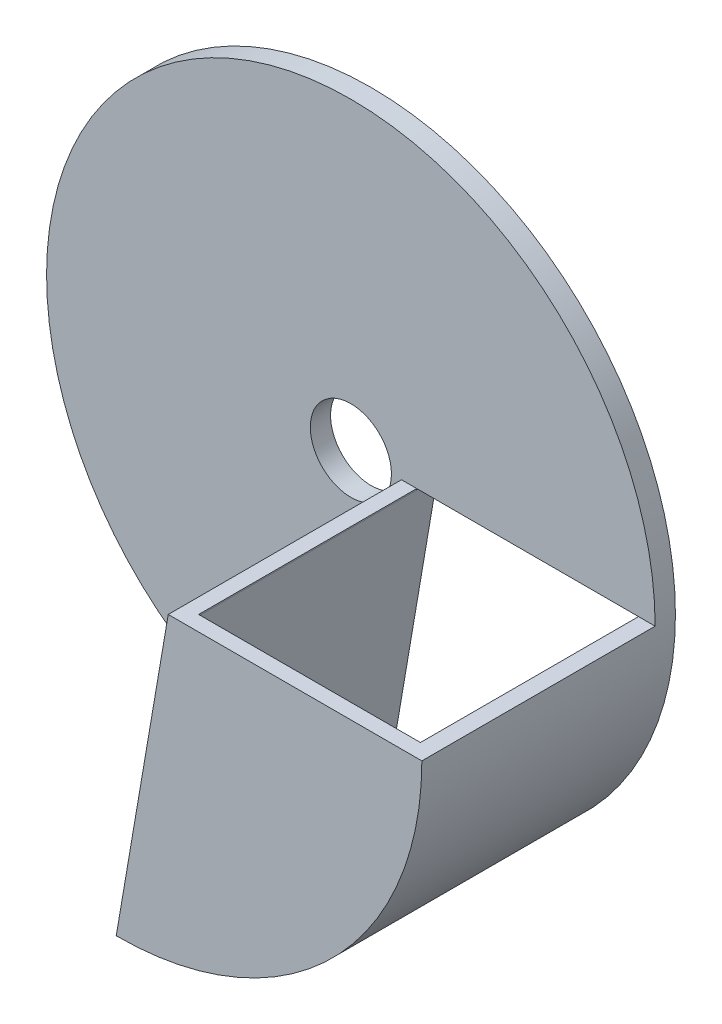
SolidWorks part; units mm, degrees
note: The reader was unsure of these and kept them because the rebuilt part matched: shared geometry of "Sketch1<3>", "Sketch1<6>".
ref_plane "Front Plane" through (0, 0, 0) normal (0, 0, 1) x (1, 0, 0)
ref_plane "Top Plane" through (0, 0, 0) normal (0, 1, 0) x (1, 0, 0)
ref_plane "Right Plane" through (0, 0, 0) normal (1, 0, 0) x (0, 0, -1)
sketch "Sketch1" plane through (0, 0, 0) normal (0, 0, 1) x (1, 0, 0)
  line L0 (60, 0) -> (9.9909, 0)
  line L1 (9.9909, 0) -> (-0.2624, -59.9994)
  line L8 (12.5217, -3) -> (13.0343, 0)
  line L12 (12.5217, -3) -> (3.3277, -56.801)
  circle A0 centre (0, 0) radius 60
  circle A1 centre (0, 0) radius 8
  arc A2 (-0.2624, -59.9994) -> (60, 0) centre (0, 0) ccw
  arc A8 (0.2658, -56.9085) -> (56.7109, 0) centre (-0.1999, 0.0004) ccw
  point P14 (-32.8158, 3)
  dimension "D1" = 120
  dimension "D2" = 3
  dimension "D3" = 180
  dimension "D4" = 60
  dimension "D6" = 3
extrude "Boss-Extrude1" add sketch "Sketch1" along normal blind 4 contours L0 A8 L1 A1 | A0 A8 L0 A2 L1
extrude "Boss-Extrude2" add sketch "Sketch1<3>" along normal blind 50 contours L1 A2 L0
sketch "Sketch1<3>" plane through (0, 0, 0) normal (0, 0, 1) x (1, 0, 0) same geometry as "Sketch1"
sketch "Sketch3" plane through (0, 0, 0) normal (0, 1, 0) x (1, 0, 0)
  line L0 (12.9909, -47) -> (12.9909, -4)
  line L8 (60, -50) -> (9.9909, -50) construction
  line L13 (56.7219, -47) -> (12.9909, -47)
  line L15 (60, -4) -> (9.9909, -4) construction
  line L16 (56.7219, -47) -> (56.7219, -4)
  line L17 (56.7219, -4) -> (12.9909, -4)
  point P6 (34.8564, -27)
  dimension "D2" = 3
extrude "Cut-Extrude1" cut sketch "Sketch1<6>" along normal blind 47
sketch "Sketch1<6>" plane through (0, 0, 0) normal (0, 0, 1) x (1, 0, 0) same geometry as "Sketch1"
extrude "Cut-Extrude3" cut sketch "Sketch3" against normal blind 3 contours L13 L0 L17 L16
